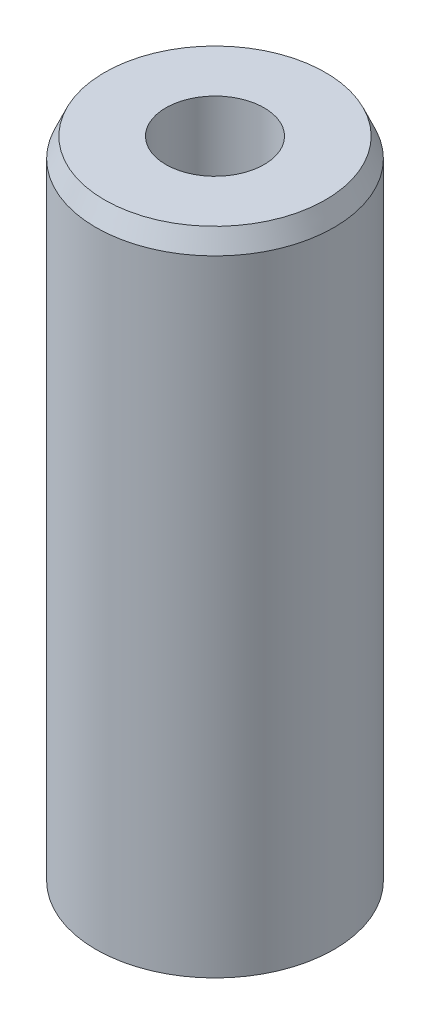
SolidWorks part; units mm, degrees
ref_plane "Front Plane" through (0, 0, 0) normal (0, 0, 1) x (1, 0, 0)
ref_plane "Top Plane" through (0, 0, 0) normal (0, 1, 0) x (1, 0, 0)
ref_plane "Right Plane" through (0, 0, 0) normal (1, 0, 0) x (0, 0, -1)
sketch "Sketch1" plane through (0, 0, 0) normal (0, 1, 0) x (1, 0, 0)
  circle A0 centre (0, 0) radius 25
  dimension "SHAFT_OD" = 50
extrude "Boss-Extrude1" add sketch "Sketch1" along normal blind 137.2038
sketch "Sketch2" plane through (0, 0, 0) normal (0, 1, 0) x (1, 0, 0)
  circle A0 centre (0, 0) radius 10.326
  dimension "BORE_D" = 20.6519
extrude "Cut-Extrude1" cut sketch "Sketch2" along normal through all
chamfer "Chamfer1" distance 4.1074 angle 23.801 2 edges at (0, 137.2038, 25) (0, 0, 25) first distance on face at (0, 137.2038, 25) first distance on face at (0, 0, 10.326)
